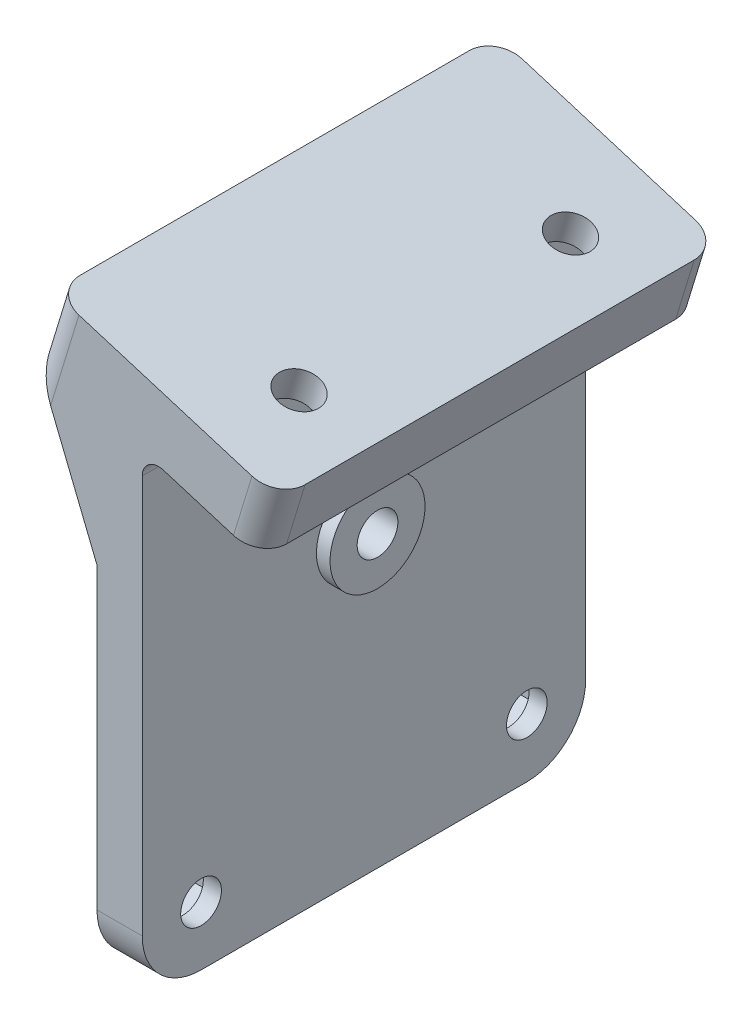
SolidWorks part; units mm, degrees
ref_plane "Plan de face" through (0, 0, 0) normal (0, 0, 1) x (1, 0, 0)
ref_plane "Plan de dessus" through (0, 0, 0) normal (0, 1, 0) x (1, 0, 0)
ref_plane "Plan de droite" through (0, 0, 0) normal (1, 0, 0) x (0, 0, -1)
sketch "Esquisse1" plane through (0, 0, 0) normal (0, 0, 1) x (1, 0, 0)
  line L0 (0, 0) -> (-24.8639, 7.6017)
  line L1 (-24.8639, 7.6017) -> (-26.9105, 0.9075)
  line L2 (-26.9105, 0.9075) -> (-20, -1.2052)
  line L3 (-20, -1.2052) -> (-20, -71.2052)
  line L4 (-20, -71.2052) -> (-15, -71.2052)
  line L5 (-15, -71.2052) -> (-15, -2.7339)
  line L6 (-15, -2.7339) -> (-2.0466, -6.6941)
  line L7 (-2.0466, -6.6941) -> (0, 0)
  line L8 (-24.8639, 7.6017) -> (-0.4628, 7.6017) construction
  dimension "D1" = 7
  dimension "D2" = 26
  dimension "D3" = 17
  dimension "D4" = 15
  dimension "D5" = 5
  dimension "D6" = 70
extrude "Boss.-Extru.1" add sketch "Esquisse1" along normal blind 49
sketch "Esquisse2" plane through (0, 0, 0) normal (0.2924, 0.9563, 0) x (0.9563, -0.2924, 0)
  line L0 (-7.5, 0) -> (-7.5, -49) construction
  line L1 (0, 0) -> (-26, 0) construction
  line L2 (0, -49) -> (-26, -49) construction
  line L3 (0, -49) -> (0, 0) construction
  line L4 (-7.5, -24.5) -> (-17.5689, -24.5) construction
  circle A0 centre (-7.5, -9.5) radius 2.25
  circle A1 centre (-7.5, -39.5) radius 2.25
  dimension "D2" = 4.5
  dimension "D3" = 30
  dimension "D1" = 7.5
extrude "Enlèv. mat.-Extru.1" cut sketch "Esquisse2" against normal up to next and the other way through all
sketch "Esquisse3" plane through (-15, 0, 0) normal (1, 0, 0) x (0, 0, -1)
  line L0 (0, -49.2052) -> (-49, -49.2052) construction
  line L1 (0, -71.2052) -> (0, -2.7339) construction
  line L2 (-49, -71.2052) -> (-49, -2.7339) construction
  line L3 (-49, -71.2052) -> (0, -71.2052) construction
  line L4 (-24.5, -49.2052) -> (-24.5, -22.2052) construction
  circle A0 centre (-42.5, -49.2052) radius 2.25
  circle A1 centre (-6.5, -49.2052) radius 2.25
  circle A2 centre (-24.5, -22.2052) radius 2.25
  dimension "D2" = 4.5
  dimension "D3" = 36
  dimension "D4" = 27
  dimension "D1" = 22
extrude "Enlèv. mat.-Extru.2" cut sketch "Esquisse3" against normal up to next
sketch "Esquisse4" plane through (-15, 0, 0) normal (1, 0, 0) x (0, 0, -1)
  line L0 (-42.5, -49.2052) -> (-49, -49.2052) construction
  line L3 (-24.5, -71.2052) -> (-42.5, -55.7052)
  line L5 (-49, -71.2052) -> (0, -71.2052) construction
  line L6 (-42.5, -55.7052) -> (-42.5, -49.2052) construction
  line L7 (-24.5, -71.2052) -> (-24.5, -37.1138) construction
  line L8 (-6.5, -55.7052) -> (-6.5, -49.2052) construction
  line L9 (-6.5, -49.2052) -> (0, -49.2052) construction
  line L10 (-24.5, -71.2052) -> (-6.5, -55.7052)
  line L11 (-49, -49.2052) -> (-50, -49.2052)
  line L12 (-50, -49.2052) -> (-50, -72.2052)
  line L13 (-50, -72.2052) -> (1, -72.2052)
  line L14 (1, -72.2052) -> (1, -49.2052)
  line L15 (1, -49.2052) -> (0, -49.2052)
  arc A0 (-49, -49.2052) -> (-42.5, -55.7052) centre (-42.5, -49.2052) ccw
  arc A1 (0, -49.2052) -> (-6.5, -55.7052) centre (-6.5, -49.2052) cw
  dimension "D1" = 6.5
  dimension "D2" = 1
  dimension "D3" = 1
extrude "Enlèv. mat.-Extru.3" cut sketch "Esquisse4" against normal up to next (5 mm away)
fillet "Congé1" radius 3 1 edges at (-17.5, -71.2052, 24.5)
sketch "Esquisse5" plane through (0, 0, 0) normal (0.2924, 0.9563, 0) x (0.9563, -0.2924, 0)
  line L0 (0, -24.5) -> (-19.2375, -24.5) construction
  line L1 (-3.95, -11.5496) -> (-3.95, -7.4504)
  line L2 (-3.95, -7.4504) -> (-7.5, -5.4008)
  line L3 (-7.5, -5.4008) -> (-11.05, -7.4504)
  line L4 (-11.05, -7.4504) -> (-11.05, -11.5496)
  line L5 (-11.05, -11.5496) -> (-7.5, -13.5992)
  line L6 (-7.5, -13.5992) -> (-3.95, -11.5496)
  line L7 (0, -49) -> (0, 0) construction
  line L8 (-7.5, -35.4008) -> (-3.95, -37.4504)
  line L9 (-11.05, -37.4504) -> (-7.5, -35.4008)
  line L10 (-11.05, -41.5496) -> (-11.05, -37.4504)
  line L11 (-7.5, -43.5992) -> (-11.05, -41.5496)
  line L12 (-3.95, -41.5496) -> (-7.5, -43.5992)
  line L13 (-3.95, -37.4504) -> (-3.95, -41.5496)
  circle A0 centre (-7.5, -9.5) radius 3.55 construction
  circle A1 centre (-7.5, -39.5) radius 3.55 construction
  dimension "D1" = 7.1
extrude "Enlèv. mat.-Extru.4" cut sketch "Esquisse5" along normal blind 3.5 from vertex starting at point (-2.0466, -6.6941, 0)
sketch "Esquisse6" plane through (0, 0, 49) normal (0, 0, 1) x (1, 0, 0)
  line L0 (-26.9105, 0.9075) -> (-20, -16.2052)
  line L1 (-20, -1.2052) -> (-20, -49.2052) construction
  line L2 (-20, -16.2052) -> (-20, -1.2052)
  line L3 (-20, -1.2052) -> (-26.9105, 0.9075)
  dimension "D1" = 15
extrude "Boss.-Extru.2" add sketch "Esquisse6" against normal up to vertex (49 mm away) up to point (-26.9105, 0.9075, 0)
fillet "Congé2" radius 1.8 1 edges at (-15, -2.7339, 24.5)
fillet "Congé3" radius 3 4 edges at (-25.8872, 4.2546, 0) (-1.0233, -3.3471, 0) (-1.0233, -3.3471, 49) (-25.8872, 4.2546, 49)
sketch "Esquisse8" plane through (-15, 0, 0) normal (1, 0, 0) x (0, 0, -1)
  line L0 (-42.5, -55.7052) -> (-6.5, -55.7052)
  line L1 (-6.5, -55.7052) -> (-6.5, -71.7052)
  line L2 (-6.5, -71.7052) -> (-42.5, -71.7052)
  line L3 (-42.5, -71.7052) -> (-42.5, -55.7052)
  dimension "D1" = 16
extrude "Enlèv. mat.-Extru.5" cut sketch "Esquisse8" against normal through all both and the other way through all
sketch "Esquisse9" plane through (-15, 0, 0) normal (1, 0, 0) x (0, 0, -1)
  circle A0 centre (-24.5, -22.2052) radius 5.25
  circle A1 centre (-24.5, -22.2052) radius 2.25
  circle A3 centre (-24.5, -22.2052) radius 2.25 construction
  dimension "D1" = 3
extrude "Boss.-Extru.3" add sketch "Esquisse9" along normal blind 1.5
sketch "Esquisse10" plane through (-20, 0, 0) normal (-1, 0, 0) x (0, 0, 1)
  line L1 (28.05, -24.2548) -> (28.05, -20.1556)
  line L2 (28.05, -20.1556) -> (24.5, -18.106)
  line L3 (24.5, -18.106) -> (20.95, -20.1556)
  line L4 (20.95, -20.1556) -> (20.95, -24.2548)
  line L5 (20.95, -24.2548) -> (24.5, -26.3044)
  line L6 (24.5, -26.3044) -> (28.05, -24.2548)
  line L7 (10.05, -51.2548) -> (10.05, -47.1556)
  line L8 (10.05, -47.1556) -> (6.5, -45.106)
  line L9 (6.5, -45.106) -> (2.95, -47.1556)
  line L10 (2.95, -47.1556) -> (2.95, -51.2548)
  line L11 (2.95, -51.2548) -> (6.5, -53.3044)
  line L12 (6.5, -53.3044) -> (10.05, -51.2548)
  line L13 (46.05, -51.2548) -> (46.05, -47.1556)
  line L14 (46.05, -47.1556) -> (42.5, -45.106)
  line L15 (42.5, -45.106) -> (38.95, -47.1556)
  line L16 (38.95, -47.1556) -> (38.95, -51.2548)
  line L17 (38.95, -51.2548) -> (42.5, -53.3044)
  line L18 (42.5, -53.3044) -> (46.05, -51.2548)
  circle A0 centre (24.5, -22.2052) radius 3.55 construction
  circle A1 centre (6.5, -49.2052) radius 3.55 construction
  circle A2 centre (42.5, -49.2052) radius 3.55 construction
  dimension "D1" = 7.1
extrude "Enlèv. mat.-Extru.6" cut sketch "Esquisse10" against normal blind 3
